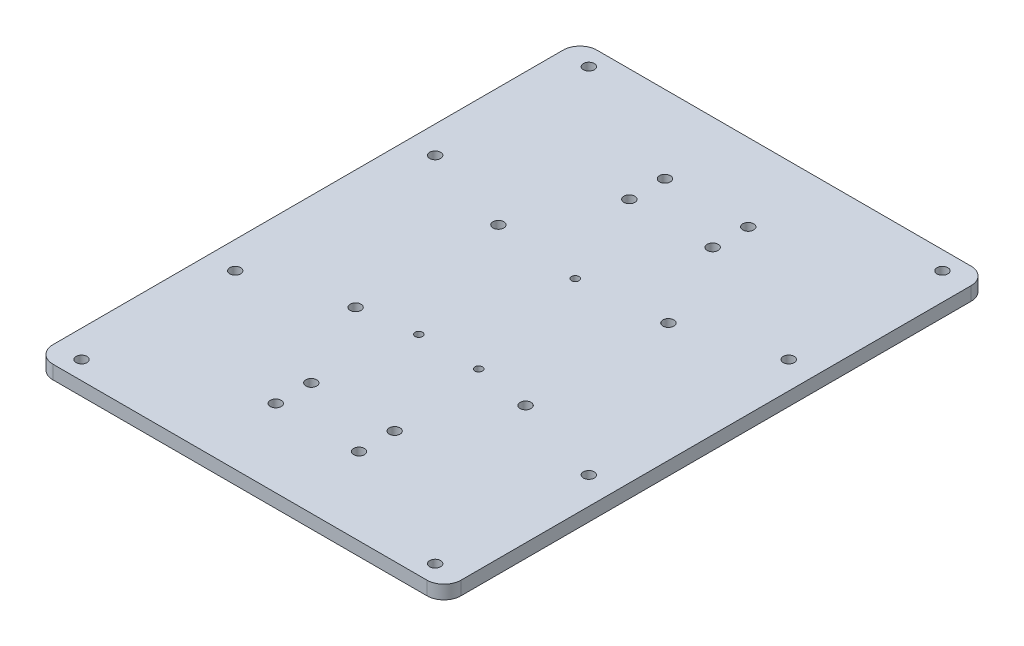
SolidWorks part; units mm, degrees
material "自定义塑料"
ref_plane "前视基准面" through (0, 0, 0) normal (0, 0, 1) x (1, 0, 0)
ref_plane "上视基准面" through (0, 0, 0) normal (0, 1, 0) x (1, 0, 0)
ref_plane "右视基准面" through (0, 0, 0) normal (1, 0, 0) x (0, 0, -1)
sketch "草图1" plane through (0, 0, 0) normal (0, 1, 0) x (1, 0, 0)
  line L0 (0, 0) -> (-20.2314, 0) construction
  line L1 (-60, 80) -> (60, 80)
  line L2 (-60, 80) -> (-60, -80)
  line L3 (-60, -80) -> (60, -80)
  line L4 (60, 80) -> (60, -80)
  line L5 (-60, 80) -> (60, -80) construction
  line L6 (-60, -80) -> (60, 80) construction
  line L7 (0, 0) -> (0, 21.0425) construction
  line L8 (-60, 52) -> (-53.3899, 52) construction
  circle A0 centre (-52, 74.6) radius 1.6
  circle A1 centre (-52, 29.4) radius 1.6
  circle A2 centre (-12.25, 57.23) radius 1.6
  circle A3 centre (-12.25, 46.77) radius 1.6
  circle A4 centre (-52, -29.4) radius 1.6
  circle A5 centre (-12.25, -46.77) radius 1.6
  circle A6 centre (-12.25, -57.23) radius 1.6
  circle A7 centre (-52, -74.6) radius 1.6
  circle A8 centre (52, -74.6) radius 1.6
  circle A9 centre (12.25, -57.23) radius 1.6
  circle A10 centre (12.25, -46.77) radius 1.6
  circle A11 centre (52, -29.4) radius 1.6
  circle A12 centre (52, 29.4) radius 1.6
  circle A13 centre (12.25, 46.77) radius 1.6
  circle A14 centre (12.25, 57.23) radius 1.6
  circle A15 centre (52, 74.6) radius 1.6
  circle A16 centre (0, 18.6) radius 1.1
  circle A17 centre (8.8, -18.6) radius 1.1
  circle A18 centre (-8.8, -18.6) radius 1.1
  circle A19 centre (-25, 21) radius 1.6
  circle A20 centre (25, 21) radius 1.6
  circle A21 centre (25, -21) radius 1.6
  circle A22 centre (-25, -21) radius 1.6
  point P0 (0, 0)
  dimension "D4" = 3.2
  dimension "D9" = 2.2
  dimension "D15" = 3.2
  dimension "D1" = 120
  dimension "D2" = 160
  dimension "D3" = 52
  dimension "D5" = 45.2
  dimension "D6" = 8
  dimension "D7" = 10.46
  dimension "D8" = 39.75
  dimension "D10" = 18.6
  dimension "D11" = 18.6
  dimension "D12" = 8.8
  dimension "D13" = 50
  dimension "D14" = 42
extrude "凸台-拉伸1" add sketch "草图1" along normal blind 4
fillet "圆角1" radius 5 4 edges at (-60, 2, -80) (60, 2, -80) (60, 2, 80) (-60, 2, 80)
